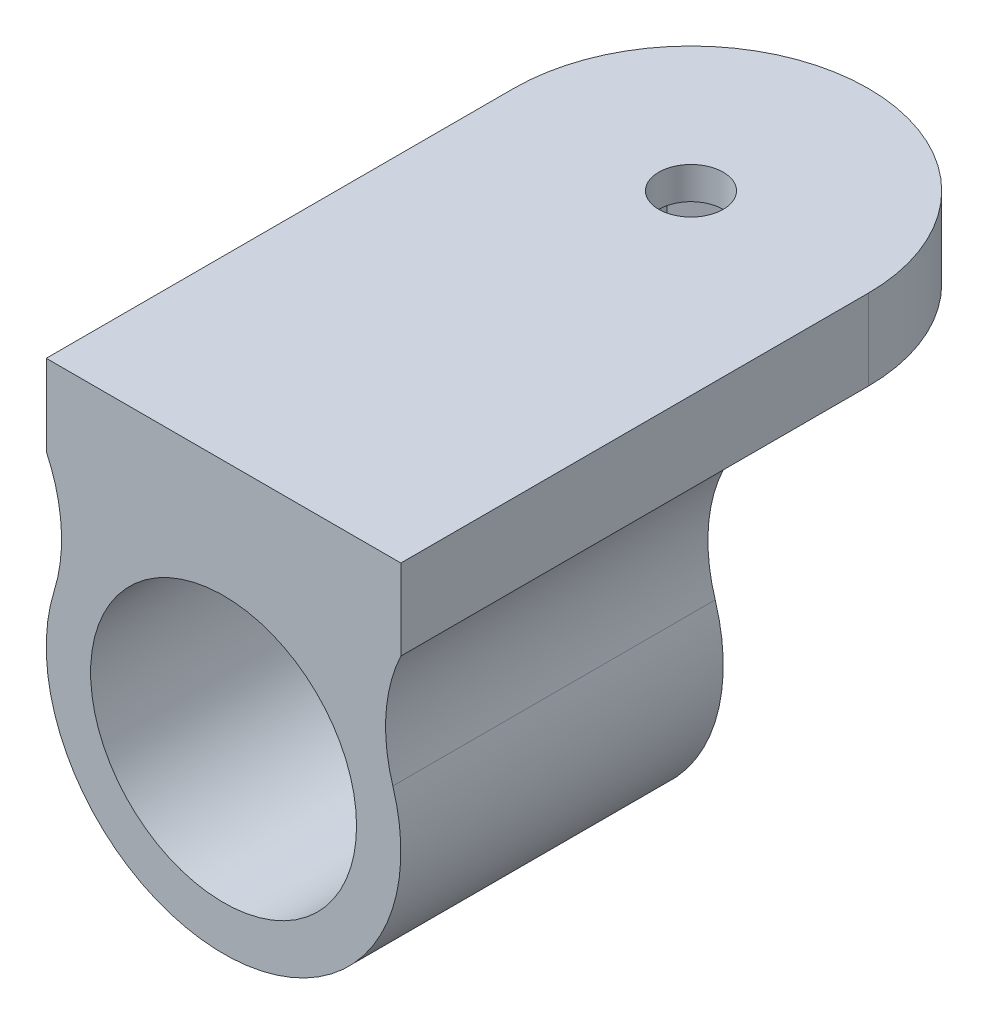
SolidWorks part; units mm, degrees
ref_plane "Front Plane" through (0, 0, 0) normal (0, 0, 1) x (1, 0, 0)
ref_plane "Top Plane" through (0, 0, 0) normal (0, 1, 0) x (1, 0, 0)
ref_plane "Right Plane" through (0, 0, 0) normal (1, 0, 0) x (0, 0, -1)
sketch "Sketch1" plane through (0, 0, 0) normal (0, 0, 1) x (1, 0, 0)
  circle A0 centre (0, 0) radius 11
  circle A1 centre (0, 0) radius 8.25
  dimension "D1" = 16.5
  dimension "D2" = 22
extrude "Boss-Extrude1" add sketch "Sketch1" along normal blind 20
sketch "Sketch2" plane through (0, 0, 0) normal (0, 1, 0) x (1, 0, 0)
  line L1 (-11, -20) -> (11, -20)
  line L2 (-11, -20) -> (-11, 20)
  line L3 (-11, 20) -> (11, 20)
  line L4 (11, -20) -> (11, 20)
  dimension "D1" = 22
  dimension "D2" = 40
extrude "Boss-Extrude2" add sketch "Sketch2" along normal blind 5 from offset 10.5
fillet "Fillet1" radius 10 2 edges at (3.2787, 10.5, 10) (-3.2787, 10.5, 10)
sketch "Sketch3" plane through (0, 10.5, 0) normal (0, -1, 0) x (1, 0, 0)
  line L0 (11, 0) -> (11, -20) construction
  line L1 (11, -20) -> (-11, -20) construction
  line L2 (-11, -20) -> (-11, 0) construction
  line L3 (-11, -9) -> (-17.5081, -13.9208)
  line L4 (-17.5081, -13.9208) -> (-14.2541, -21.5238)
  line L5 (-14.2541, -21.5238) -> (21.256, -20)
  line L6 (21.256, -20) -> (18.9579, -14.6305)
  line L7 (18.9579, -14.6305) -> (11, -9)
  circle A0 centre (0, -9) radius 2
  arc A1 (-11, -9) -> (11, -9) centre (0, -9) ccw
  dimension "D1" = 4
extrude "Cut-Extrude1" cut sketch "Sketch3" against normal through all both
sketch "Sketch4" plane through (0, 10.5, 0) normal (0, -1, 0) x (1, 0, 0)
  line L1 (3.5, -6.9793) -> (0, -4.9585)
  line L2 (0, -4.9585) -> (-3.5, -6.9793)
  line L3 (-3.5, -6.9793) -> (-3.5, -11.0207)
  line L4 (-3.5, -11.0207) -> (0, -13.0415)
  line L5 (0, -13.0415) -> (3.5, -11.0207)
  line L6 (3.5, -11.0207) -> (3.5, -6.9793)
  circle A0 centre (0, -9) radius 3.5 construction
  dimension "D1" = 7
extrude "Cut-Extrude2" cut sketch "Sketch4" against normal blind 3
